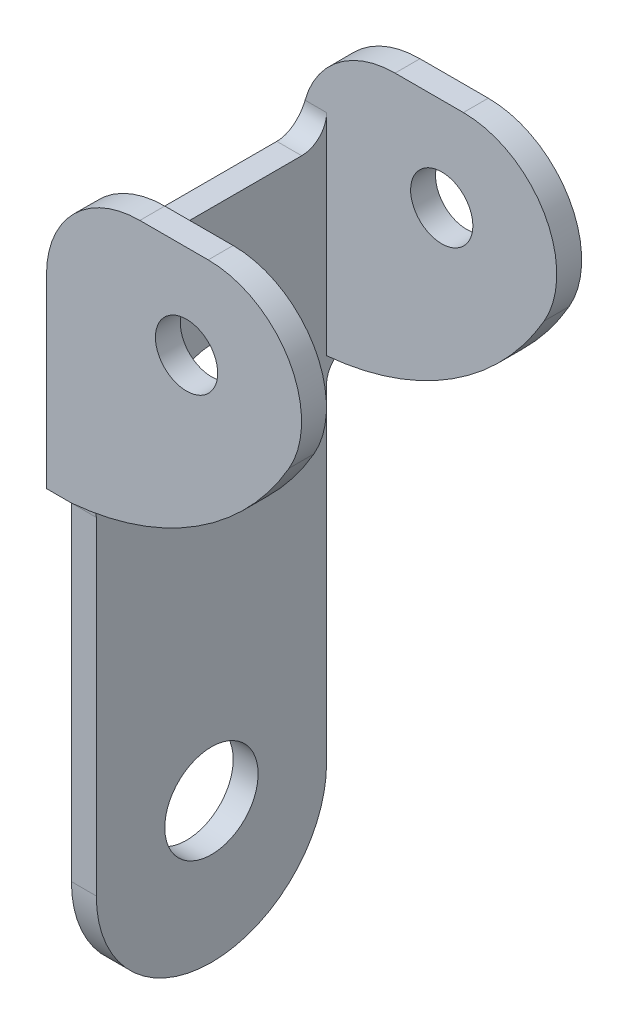
SolidWorks part; units mm, degrees
material "合金钢"
ref_plane "前视基准面" through (0, 0, 0) normal (0, 0, 1) x (1, 0, 0)
ref_plane "上视基准面" through (0, 0, 0) normal (0, 1, 0) x (1, 0, 0)
ref_plane "右视基准面" through (0, 0, 0) normal (1, 0, 0) x (0, 0, -1)
sketch "草图1" plane through (0, 0, 0) normal (0, 0, 1) x (1, 0, 0)
  line L0 (3, 0) -> (5.1962, 0)
  line L1 (0, -3) -> (0, -24)
  line L2 (0, -24) -> (0.8, -24)
  line L3 (0.8, -24) -> (0.8, -8.9644)
  circle A0 centre (4.5, -3) radius 1
  arc A1 (0.8, -8.9644) -> (7.7942, -4.5) centre (0, 0) ccw
  arc A2 (3, 0) -> (0, -3) centre (3, -3) ccw
  arc A3 (5.1962, 0) -> (7.7942, -4.5) centre (5.1962, -3) cw
  point P14 (9, 0)
  dimension "D2" = 2
  dimension "D3" = 4.5
  dimension "D7" = 3
  dimension "D1" = 9
  dimension "D4" = 3
  dimension "D5" = 24
  dimension "D6" = 0.8
extrude "凸台-拉伸1" add sketch "草图1" along normal blind 9
sketch "草图2" plane through (0.8, 0, 0) normal (1, 0, 0) x (0, 0, -1)
  line L0 (-9, -8.9644) -> (0, -8.9644) construction
  line L1 (-8.2, -8.9644) -> (-0.8, -8.9644)
  line L2 (-8.2, -8.9644) -> (-8.2, 1.0356)
  line L3 (-8.2, 1.0356) -> (-0.8, 1.0356)
  line L4 (-0.8, -8.9644) -> (-0.8, 1.0356)
  line L5 (0, -4.5) -> (0, 0) construction
  line L6 (-9, 0) -> (-9, -4.5) construction
  dimension "D1" = 0.8
  dimension "D2" = 0.8
  dimension "D3" = 10
extrude "切除-拉伸1" cut sketch "草图2" along normal blind 9
sketch "草图3" plane through (0.8, 0, 0) normal (1, 0, 0) x (0, 0, -1)
  line L0 (-8.2, -8.9644) -> (-8.2, -4.5) construction
  line L1 (-8.2, -8.9644) -> (-9, -8.9644)
  line L2 (-8.2, -8.9644) -> (-8.2, -24)
  line L3 (-8.2, -24) -> (-9, -24)
  line L4 (-9, -8.9644) -> (-9, -24)
  line L5 (-8.2, -0.9604) -> (-8.2, -8.9644) construction
  line L7 (-0.8, -8.9644) -> (0, -8.9644)
  line L8 (-0.8, -8.9644) -> (-0.8, -24)
  line L9 (-0.8, -24) -> (0, -24)
  line L10 (0, -8.9644) -> (0, -24)
extrude "切除-拉伸2" cut sketch "草图3" against normal blind 9
fillet "圆角2" radius 3.7 2 edges at (0.4, -24, 0.8) (0.4, -24, 8.2)
sketch "草图4" plane through (0, 0, 0) normal (-1, 0, 0) x (0, 0, 1)
  line L0 (9, -3) -> (0, -3) construction
  line L1 (0.8, -0.9604) -> (8.2, -0.9604)
  line L2 (0.8, -0.9604) -> (0.8, -3)
  line L3 (0.8, -3) -> (8.2, -3)
  line L4 (8.2, -0.9604) -> (8.2, -3)
  line L5 (8.2, 0) -> (8.2, -0.9604) construction
extrude "切除-拉伸3" cut sketch "草图4" against normal blind 9
sketch "草图5" plane through (0.8, 0, 0) normal (1, 0, 0) x (0, 0, -1)
  line L0 (-0.8, -3) -> (-8.2, -3) construction
  line L2 (-0.8, -8.9644) -> (-0.8, -20.3) construction
  circle A0 centre (-4.5, -8.3) radius 1.5
  circle A1 centre (-4.5, -19.5) radius 1.5
  dimension "D1" = 3
  dimension "D2" = 5.3
  dimension "D3" = 3
  dimension "D4" = 11.2
  dimension "D5" = 3.7
extrude "切除-拉伸4" cut sketch "草图5" against normal blind 9
fillet "圆角3" radius 0.8 4 edges at (0.4, -8.9644, 0.8) (0.4, -8.9644, 8.2) (0.4, -3, 0.8) (0.4, -3, 8.2)
